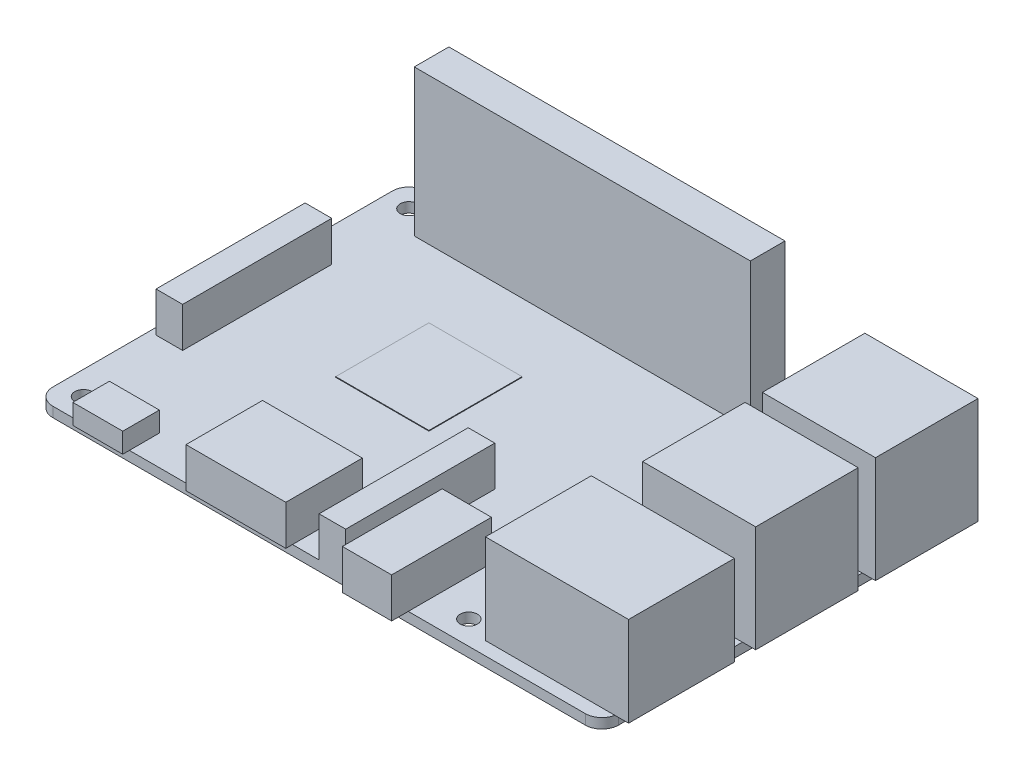
SolidWorks part; units mm, degrees
ref_plane "Front Plane" through (0, 0, 0) normal (0, 0, 1) x (1, 0, 0)
ref_plane "Top Plane" through (0, 0, 0) normal (0, 1, 0) x (1, 0, 0)
ref_plane "Right Plane" through (0, 0, 0) normal (1, 0, 0) x (0, 0, -1)
sketch "Sketch1" plane through (0, 0, 0) normal (0, 1, 0) x (1, 0, 0)
  line L1 (-42.5, -28) -> (42.5, -28)
  line L2 (-42.5, -28) -> (-42.5, 28)
  line L3 (-42.5, 28) -> (42.5, 28)
  line L4 (42.5, -28) -> (42.5, 28)
  line L5 (-42.5, -28) -> (42.5, 28) construction
  line L6 (-42.5, 28) -> (42.5, -28) construction
  point P0 (0, 0)
  dimension "D1" = 56
  dimension "D2" = 85
extrude "Boss-Extrude1" add sketch "Sketch1" along normal blind 1.5
fillet "Fillet1" radius 2.5 4 edges at (-42.5, 0.75, 28) (-42.5, 0.75, -28) (42.5, 0.75, -28) (42.5, 0.75, 28)
sketch "Sketch2" plane through (0, 1.5, 0) normal (0, 1, 0) x (1, 0, 0)
  line L0 (-42.5, 25.5) -> (-42.5, -25.5) construction
  line L2 (40, 28) -> (-40, 28) construction
  line L3 (-38.95, -24.45) -> (-38.95, 24.45) construction
  line L5 (-40, -28) -> (40, -28) construction
  line L6 (-38.95, 24.45) -> (18.95, 24.45) construction
  line L7 (18.95, 24.45) -> (18.95, -24.45) construction
  line L8 (18.95, -24.45) -> (-38.95, -24.45) construction
  circle A0 centre (-38.95, -24.45) radius 1.3
  circle A1 centre (-38.95, 24.45) radius 1.3
  circle A2 centre (18.95, 24.45) radius 1.3
  circle A3 centre (18.95, -24.45) radius 1.3
  dimension "D1" = 2.6
  dimension "D2" = 51.5
  dimension "D3" = 2.25
  dimension "D4" = 2.25
  dimension "D5" = 2.25
  dimension "D6" = 60.5
extrude "Cut-Extrude1" cut sketch "Sketch2" against normal through all
sketch "Sketch3" plane through (0, 1.5, 0) normal (0, 1, 0) x (1, 0, 0)
  line L0 (-42.5, 25.5) -> (-42.5, -25.5) construction
  line L1 (-22.5, 11) -> (-8.5, 11)
  line L2 (-22.5, 11) -> (-22.5, -3)
  line L3 (-22.5, -3) -> (-8.5, -3)
  line L4 (-8.5, 11) -> (-8.5, -3)
  line L5 (-40, -28) -> (40, -28) construction
  dimension "D1" = 14
  dimension "D2" = 20
  dimension "D3" = 25
extrude "Boss-Extrude2" add sketch "Sketch3" along normal blind 0.1
sketch "Sketch4" plane through (0, 1.5, 0) normal (0, 1, 0) x (1, 0, 0)
  line L0 (-42.5, 25.5) -> (-42.5, -25.5) construction
  line L1 (-35, 26.5) -> (15.5, 26.5)
  line L2 (-35, 26.5) -> (-35, 21.3)
  line L3 (-35, 21.3) -> (15.5, 21.3)
  line L4 (15.5, 26.5) -> (15.5, 21.3)
  line L5 (40, 28) -> (-40, 28) construction
  dimension "D1" = 5.2
  dimension "D2" = 7.5
  dimension "D3" = 1.5
  dimension "D4" = 50.5
extrude "Boss-Extrude3" add sketch "Sketch4" along normal blind 22
sketch "Sketch5" plane through (0, 1.5, 0) normal (0, 1, 0) x (1, 0, 0)
  line L0 (-42.5, 25.5) -> (-42.5, -25.5) construction
  line L1 (-36, -23.5) -> (-28.5, -23.5)
  line L2 (-36, -23.5) -> (-36, -29)
  line L3 (-36, -29) -> (-28.5, -29)
  line L4 (-28.5, -23.5) -> (-28.5, -29)
  line L5 (-40, -28) -> (40, -28) construction
  dimension "D1" = 7.5
  dimension "D2" = 6.5
  dimension "D3" = 5.5
  dimension "D4" = 1
extrude "Boss-Extrude4" add sketch "Sketch5" along normal blind 3
sketch "Sketch6" plane through (0, 1.5, 0) normal (0, 1, 0) x (1, 0, 0)
  line L0 (-28.5, -28) -> (40, -28) construction
  line L1 (0, -5.6) -> (4, -5.6)
  line L2 (0, -5.6) -> (0, -28)
  line L3 (0, -28) -> (4, -28)
  line L4 (4, -5.6) -> (4, -28)
  line L5 (-28.5, -28) -> (-28.5, -23.5) construction
  line L6 (-41.5, 11.4) -> (-37.5, 11.4)
  line L7 (-41.5, 11.4) -> (-41.5, -11)
  line L8 (-41.5, -11) -> (-37.5, -11)
  line L9 (-37.5, 11.4) -> (-37.5, -11)
  line L10 (-19, -17.5) -> (-4, -17.5)
  line L11 (-19, -17.5) -> (-19, -29)
  line L12 (-19, -29) -> (-4, -29)
  line L13 (-4, -17.5) -> (-4, -29)
  line L14 (-42.5, 25.5) -> (-42.5, -25.5) construction
  line L15 (6, -15.5) -> (13.4, -15.5)
  line L16 (6, -15.5) -> (6, -30.5)
  line L17 (6, -30.5) -> (13.4, -30.5)
  line L18 (13.4, -15.5) -> (13.4, -30.5)
  line L19 (40, 28) -> (-40, 28) construction
  dimension "D1" = 1
  dimension "D2" = 15
  dimension "D3" = 9.5
  dimension "D4" = 11.5
  dimension "D5" = 22.4
  dimension "D6" = 4
  dimension "D7" = 4
  dimension "D8" = 1
  dimension "D9" = 39
  dimension "D10" = 15
  dimension "D11" = 2
  dimension "D12" = 2.5
  dimension "D13" = 7.4
extrude "Boss-Extrude5" add sketch "Sketch6" along normal blind 6
sketch "Sketch7" plane through (0, 1.5, 0) normal (0, 1, 0) x (1, 0, 0)
  line L0 (44.5, 11.1) -> (44.5, 8.5) construction
  line L1 (23, -10.1) -> (44.5, -10.1)
  line L2 (23, -10.1) -> (23, -26)
  line L3 (23, -26) -> (44.5, -26)
  line L4 (44.5, -10.1) -> (44.5, -26)
  line L5 (27.5, 26.5) -> (44.5, 26.5)
  line L6 (27.5, 26.5) -> (27.5, 11.1)
  line L7 (27.5, 11.1) -> (44.5, 11.1)
  line L8 (44.5, 26.5) -> (44.5, 11.1)
  line L9 (27.5, 8.5) -> (44.5, 8.5)
  line L10 (27.5, 8.5) -> (27.5, -6.9)
  line L11 (27.5, -6.9) -> (44.5, -6.9)
  line L12 (44.5, 8.5) -> (44.5, -6.9)
  line L13 (44.5, -6.9) -> (44.5, -10.1) construction
  line L14 (42.5, -25.5) -> (42.5, 25.5) construction
  line L15 (40, 28) -> (-40, 28) construction
  line L16 (13.4, -28) -> (40, -28) construction
  dimension "D1" = 17
  dimension "D2" = 2
  dimension "D3" = 15.4
  dimension "D4" = 1.5
  dimension "D5" = 2.6
  dimension "D6" = 21.5
  dimension "D7" = 3.2
  dimension "D8" = 2
extrude "Boss-Extrude6" add sketch "Sketch7" along normal blind 13.5 contours L1 L4 L3 L2
extrude "Boss-Extrude7" add sketch "Sketch7<3>" along normal blind 16 contours L6 L7 L8 L5 | L10 L11 L12 L9
sketch "Sketch7<3>" plane through (0, 1.5, 0) normal (0, 1, 0) x (1, 0, 0) same geometry as "Sketch7"
